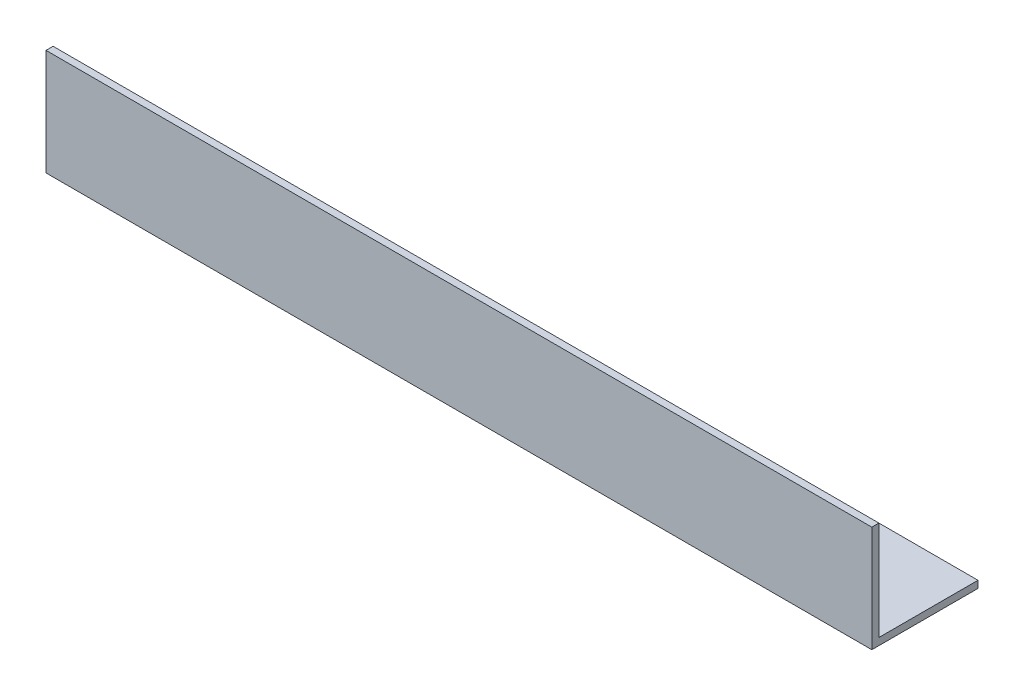
SolidWorks part; units mm, degrees
ref_plane "Спереди" through (0, 0, 0) normal (0, 0, 1) x (1, 0, 0)
ref_plane "Сверху" through (0, 0, 0) normal (0, 1, 0) x (1, 0, 0)
ref_plane "Справа" through (0, 0, 0) normal (1, 0, 0) x (0, 0, -1)
sketch "Эскиз1" plane through (0, 0, 0) normal (1, 0, 0) x (0, 0, -1)
  line L0 (0, 0) -> (0, 45)
  line L1 (0, 0) -> (45, 0)
  dimension "D1" = 45
extrude "Вытянуть-Тонкостенный1" add sketch "Эскиз1" along normal blind 350 thin thin type one direction reverse wall 3
